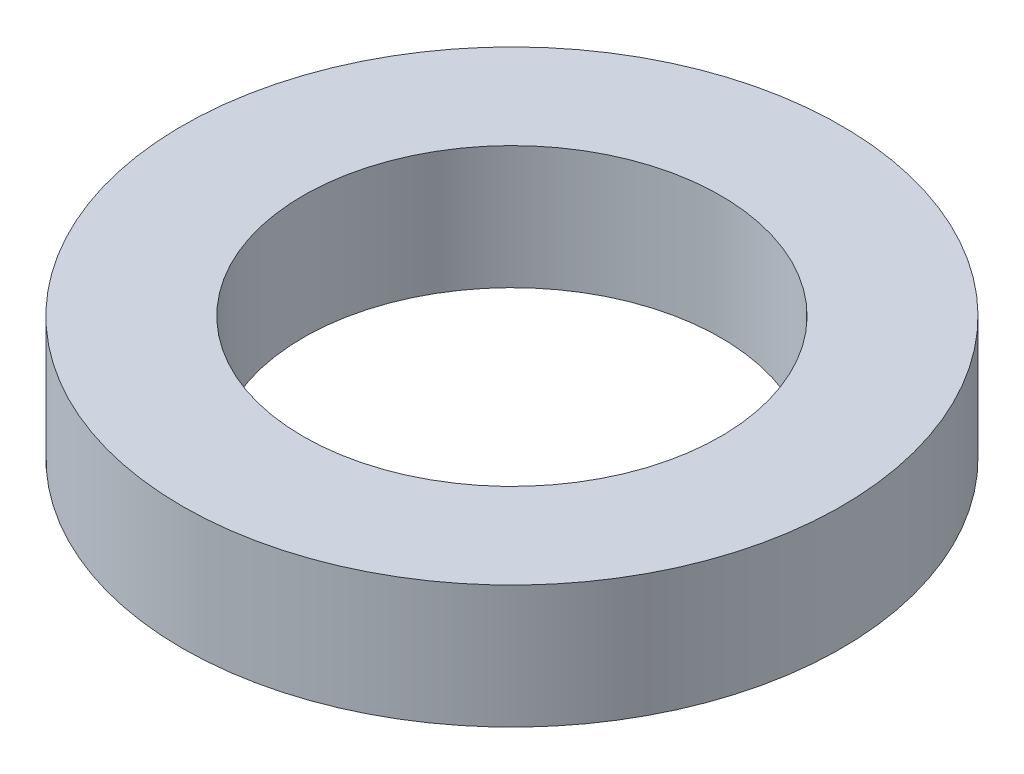
SolidWorks part; units mm, degrees
ref_plane "Front Plane" through (0, 0, 0) normal (0, 0, 1) x (1, 0, 0)
ref_plane "Top Plane" through (0, 0, 0) normal (0, 1, 0) x (1, 0, 0)
ref_plane "Right Plane" through (0, 0, 0) normal (1, 0, 0) x (0, 0, -1)
sketch "Sketch1" plane through (0, 0, 0) normal (0, 1, 0) x (1, 0, 0)
  circle A0 centre (0, 0) radius 75
  dimension "FLANGE_OD" = 150
extrude "Boss-Extrude1" add sketch "Sketch1" along normal blind 28
sketch "Sketch2" plane through (0, 0, 0) normal (0, 1, 0) x (1, 0, 0)
  circle A0 centre (0, 0) radius 47.5
  dimension "BORE_D" = 95
extrude "Cut-Extrude1" cut sketch "Sketch2" along normal through all
sketch "Sketch3" plane through (0, 28, 0) normal (0, 1, 0) x (1, 0, 0)
  circle A0 centre (0, 0) radius 31.9284 construction
  circle A1 centre (-31.9284, 0) radius 4.6509
  dimension "BOLT_D" = 9.3018
  dimension "BOLT_PCD" = 63.8567
extrude "Cut-Extrude2" cut sketch "Sketch3" against normal blind 24.5143 rebuild error yes
pattern_circular "CirPattern1" count 5 over 360 rebuild error yes
